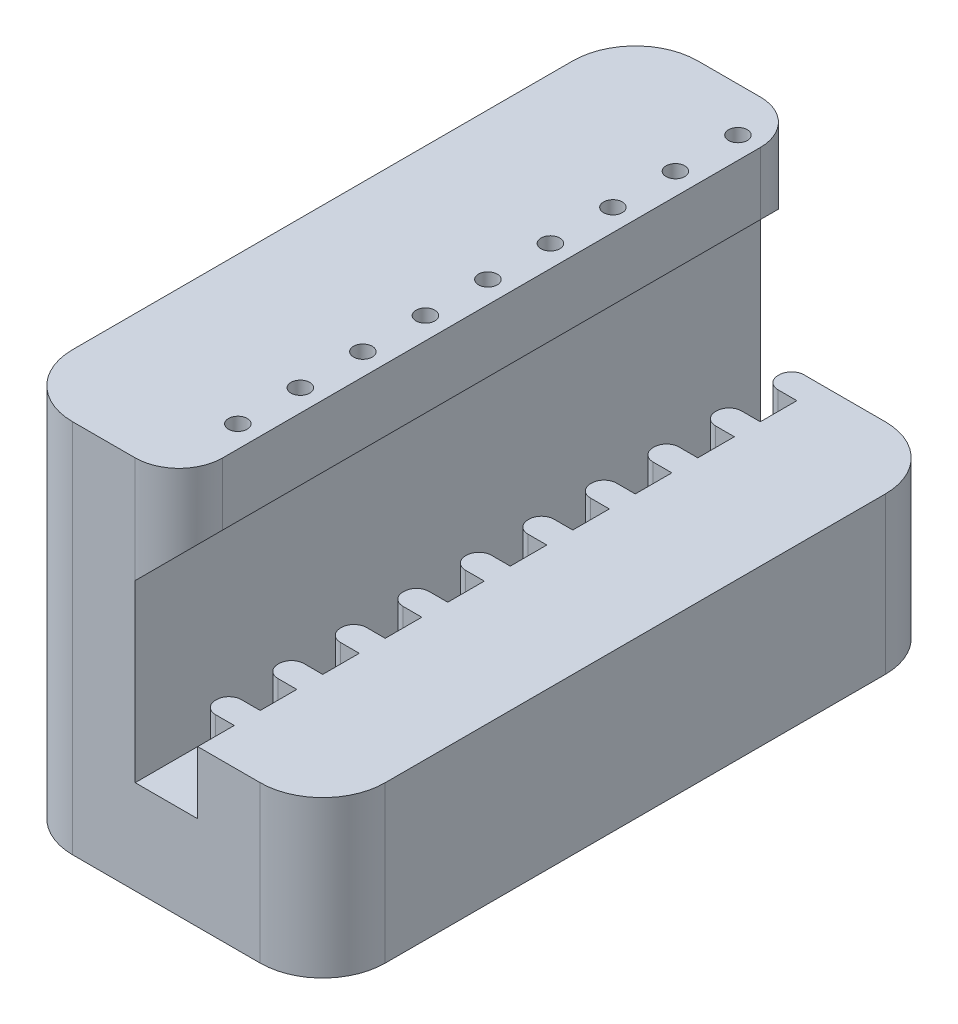
SolidWorks part; units mm, degrees
ref_plane "Front Plane" through (0, 0, 0) normal (0, 0, 1) x (1, 0, 0)
ref_plane "Top Plane" through (0, 0, 0) normal (0, 1, 0) x (1, 0, 0)
ref_plane "Right Plane" through (0, 0, 0) normal (1, 0, 0) x (0, 0, -1)
sketch "Sketch1" plane through (0, 0, 0) normal (0, 1, 0) x (1, 0, 0)
  line L1 (-5, 10) -> (5, 10)
  line L2 (-5, 10) -> (-5, -10)
  line L3 (-5, -10) -> (5, -10)
  line L4 (5, 10) -> (5, -10)
  line L5 (-5, 10) -> (5, -10) construction
  line L6 (-5, -10) -> (5, 10) construction
  point P0 (0, 0)
  dimension "D1" = 10
  dimension "D2" = 20
extrude "Boss-Extrude1" add sketch "Sketch1" along normal blind 3
sketch "Sketch2" plane through (0, 3, 0) normal (0, 1, 0) x (1, 0, 0)
  line L0 (-1, 10) -> (-5, 10)
  line L2 (1, -10) -> (1, 10)
  line L4 (5, -10) -> (5, 10)
  line L5 (5, 10) -> (-5, 10)
  line L6 (-5, 10) -> (-5, -10)
  line L7 (-5, -10) -> (5, -10)
  line L8 (5, -10) -> (5, 10)
  line L9 (5, 10) -> (1, 10)
  line L10 (-5, 10) -> (-5, -10)
  line L11 (-5, -10) -> (-1, -10)
  line L12 (-1, -10) -> (-1, 10)
  line L13 (1, -10) -> (-1, 10) construction
  line L14 (1, 10) -> (-1, -10) construction
  line L15 (1, -10) -> (5, -10)
  point P2 (0, 0)
  dimension "D2" = 2
  dimension "D1" = 0
extrude "Boss-Extrude2" add sketch "Sketch2" along normal blind 2
sketch "Sketch3" plane through (0, 3, 0) normal (0, 1, 0) x (1, 0, 0)
  line L1 (1, 10) -> (0, 10)
  line L2 (1, 10) -> (1, 9.17)
  line L3 (1, 9.17) -> (0, 9.17)
  line L4 (0, 10) -> (0, 9.17)
  dimension "D1" = 0.83
  dimension "D2" = 1
extrude "Boss-Extrude3" add sketch "Sketch3" along normal blind 2
fillet "Fillet1" radius 0.4 2 edges at (0, 4, -10) (0, 4, -9.17)
fillet "Fillet2" radius 2 4 edges at (-5, 2.5, 10) (5, 2.5, 10) (5, 2.5, -10) (-5, 2.5, -10)
sketch "Sketch6" plane through (0, 5, 0) normal (0, 1, 0) x (1, 0, 0)
  line L4 (-5, 8) -> (-5, -8)
  line L5 (-3, -10) -> (-1, -10)
  line L6 (-1, -10) -> (-1, 10)
  line L7 (-1, 10) -> (-3, 10)
  line L8 (-5, 8) -> (-5, -8)
  line L9 (-3, -10) -> (-1, -10)
  line L10 (-1, -10) -> (-1, 10)
  line L11 (-1, 10) -> (-3, 10)
  arc A2 (-5, -8) -> (-3, -10) centre (-3, -8) ccw
  arc A3 (-3, 10) -> (-5, 8) centre (-3, 8) ccw
  arc A4 (-5, -8) -> (-3, -10) centre (-3, -8) ccw
  arc A5 (-3, 10) -> (-5, 8) centre (-3, 8) ccw
  dimension "D1" = 0
extrude "Boss-Extrude4" add sketch "Sketch6" along normal blind 5
sketch "Sketch8" plane through (0, 10, 0) normal (0, 1, 0) x (1, 0, 0)
  line L0 (3, 10) -> (0.4, 10) construction
  line L3 (1, 9.17) -> (1, -10) construction
  line L4 (1, 9.17) -> (1, 8) construction
  line L6 (-1, -10) -> (-1, 10) construction
  line L7 (-1, -10) -> (1, -10) construction
  line L8 (-1, 10) -> (0.4, 10)
  line L10 (-1, -10) -> (0.4, -10)
  line L11 (-5, 8) -> (-5, -8)
  line L12 (-3, -10) -> (-1, -10)
  line L13 (-1, -10) -> (-1, 10)
  line L14 (-1, 10) -> (-3, 10)
  line L15 (-5, 8) -> (-5, -8)
  line L16 (-3, -10) -> (-1, -10)
  line L18 (-1, 10) -> (-3, 10)
  line L19 (0.4, 10) -> (0.4, -10)
  circle A0 centre (-0.3, 8.585) radius 0.3 construction
  arc A2 (-3, 10) -> (-5, 8) centre (-3, 8) ccw
  arc A3 (-5, -8) -> (-3, -10) centre (-3, -8) ccw
  arc A4 (-3, 10) -> (-5, 8) centre (-3, 8) ccw
  arc A5 (-5, -8) -> (-3, -10) centre (-3, -8) ccw
  point P4 (-0.3, 8.585)
  point P10 (1, 8.585)
  dimension "D4" = 0.6
  dimension "D1" = 2
  dimension "D2" = 0.7
  dimension "D5" = 1.4
  dimension "D3" = 0
extrude "Boss-Extrude5" add sketch "Sketch8" along normal blind 2
sketch "Sketch9" plane through (0, 10, 0) normal (0, -1, 0) x (1, 0, 0)
  circle A0 centre (-0.3, -8.585) radius 0.3 construction
  circle A1 centre (-0.3, -8.585) radius 0.3
extrude "Cut-Extrude1" cut sketch "Sketch9" against normal through all
pattern_linear "LPattern1" count 10 spacing 2 along (0, 0, 1) of "Boss-Extrude3", "Fillet1"
pattern_linear "LPattern2" count 9 spacing 2 along (0, 0, 1) of "Cut-Extrude1"
fillet "Fillet3" radius 1.4 2 edges at (0.4, 11, 10) (0.4, 11, -10)
chamfer "Chamfer1" distance 1.4 angle 45 1 edges at (-1, 10, 0)
